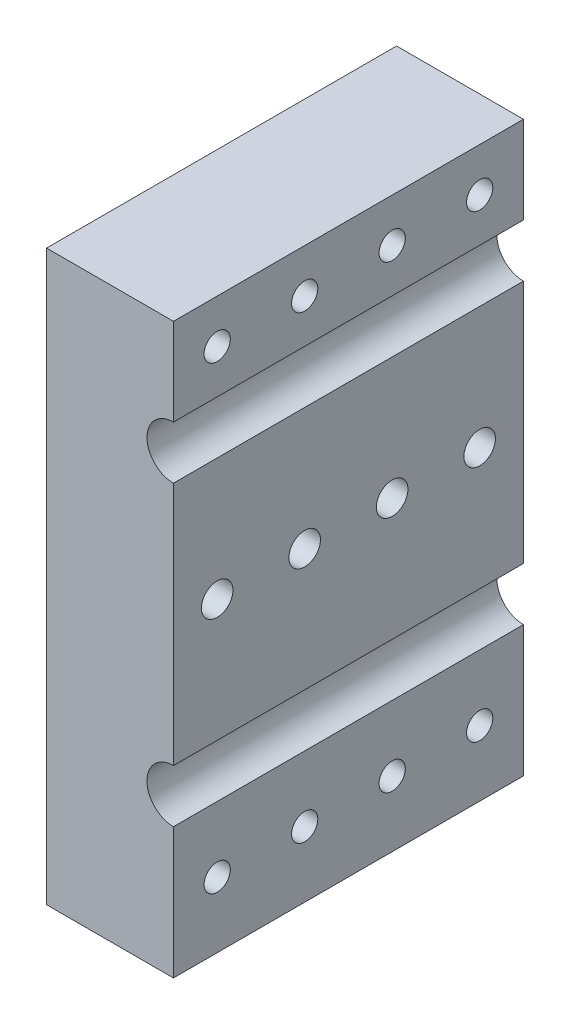
SolidWorks part; units mm, degrees
ref_plane "前视基准面" through (0, 0, 0) normal (0, 0, 1) x (1, 0, 0)
ref_plane "上视基准面" through (0, 0, 0) normal (0, 1, 0) x (1, 0, 0)
ref_plane "右视基准面" through (0, 0, 0) normal (1, 0, 0) x (0, 0, -1)
sketch "草图1" plane through (0, 0, 0) normal (0, 0, 1) x (1, 0, 0)
  line L1 (0, 0) -> (29, 0)
  line L2 (0, 0) -> (0, 65)
  line L3 (0, 65) -> (29, 65)
  line L4 (29, 0) -> (29, 65)
extrude "凸台-拉伸1" add sketch "草图1" along normal blind 40
sketch "草图2" plane through (0, 0, 40) normal (0, 0, 1) x (1, 0, 0)
  line L0 (0, 0) -> (29, 0) construction
  circle A0 centre (14.5, 52) radius 3.005
  circle A1 centre (14.5, 18) radius 3.005
  circle A2 centre (14.5, 52) radius 3.025
  circle A3 centre (14.5, 18) radius 3.025
  dimension "D1" = 0.02
  dimension "D2" = 34
  dimension "D3" = 18
extrude "切除-拉伸3" cut sketch "草图2" against normal through all
sketch "草图6" plane through (0, 0, 40) normal (0, 0, 1) x (1, 0, 0)
  line L0 (29, 65) -> (0, 65) construction
  line L1 (14.5, 65) -> (29, 65)
  line L2 (14.5, 65) -> (14.5, 0)
  line L3 (14.5, 0) -> (29, 0)
  line L4 (29, 65) -> (29, 0)
extrude "切除-拉伸4" cut sketch "草图6" against normal through all
sketch "草图7" plane through (14.5, 0, 0) normal (1, 0, 0) x (0, 0, -1)
  line L0 (-40, 65) -> (-40, 55.025) construction
  circle A0 centre (-35, 60.0125) radius 1.5
  circle A1 centre (-25, 60.0125) radius 1.5
  circle A2 centre (-5, 60.0125) radius 1.5
  circle A3 centre (-15, 60.0125) radius 1.5
  point P10 (-7.1712, 60.0125)
  dimension "D1" = 3
  dimension "D4" = 10
  dimension "D2" = 5
  dimension "D3" = 10
  dimension "D5" = 10
extrude "切除-拉伸5" cut sketch "草图7" against normal through all
sketch "草图8" plane through (14.5, 0, 0) normal (1, 0, 0) x (0, 0, -1)
  line L0 (-40, 48.975) -> (-40, 21.025) construction
  circle A0 centre (-35, 35) radius 1.8048
  circle A1 centre (-25, 35) radius 1.8048
  circle A2 centre (-15, 35) radius 1.8048
  circle A3 centre (-5, 35) radius 1.8048
  dimension "D1" = 5
  dimension "D2" = 10
  dimension "D3" = 10
  dimension "D4" = 10
extrude "切除-拉伸6" cut sketch "草图8" against normal through all
sketch "草图9" plane through (14.5, 0, 0) normal (1, 0, 0) x (0, 0, -1)
  line L0 (-40, 14.975) -> (-40, 0) construction
  circle A0 centre (-35, 7.4875) radius 1.5
  circle A1 centre (-25, 7.4875) radius 1.5
  circle A2 centre (-15, 7.4875) radius 1.5
  circle A3 centre (-5, 7.4875) radius 1.5
  dimension "D4" = 10
  dimension "D5" = 3
  dimension "D1" = 5
  dimension "D2" = 10
  dimension "D3" = 10
extrude "切除-拉伸7" cut sketch "草图9" against normal through all
